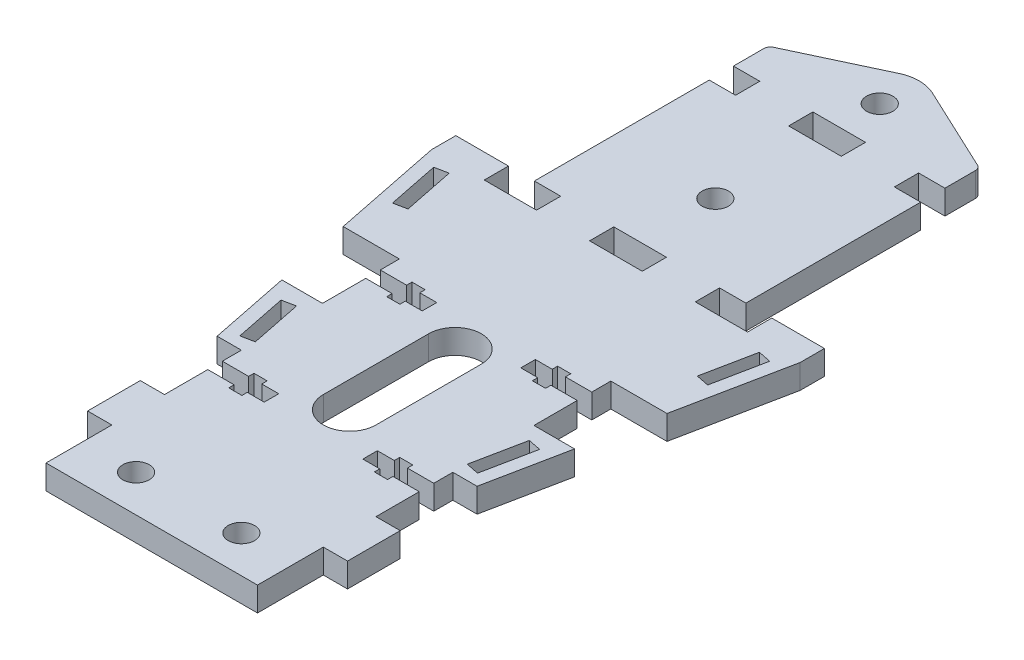
SolidWorks part; units mm, degrees
ref_plane "Front Plane" through (0, 0, 0) normal (0, 0, 1) x (1, 0, 0)
ref_plane "Top Plane" through (0, 0, 0) normal (0, 1, 0) x (1, 0, 0)
ref_plane "Right Plane" through (0, 0, 0) normal (1, 0, 0) x (0, 0, -1)
sketch "Sketch1" plane through (0, 0, 0) normal (0, 1, 0) x (1, 0, 0)
  line L0 (0, 90.3512) -> (0, 26.7242) construction
  line L1 (31.75, 26.7242) -> (25.5, 26.7242)
  line L2 (25.5, -85.217) -> (25.5, -69.342)
  line L3 (-25.5, -76.2964) -> (25.5, -76.2964) construction
  line L4 (0, 26.7242) -> (0, -76.2964) construction
  line L5 (25.5, -88.9) -> (-25.5, 88.9) construction
  line L6 (25.5, 88.9) -> (-25.5, -88.9) construction
  line L7 (-25.5, 77.6512) -> (25.5, 77.6512) construction
  line L8 (-25.5, -85.217) -> (-25.5, -69.342)
  line L9 (-25.5, 88.9) -> (-4.0485, 98.973)
  line L10 (-25.5, 80.5722) -> (-25.5, 88.9)
  line L11 (4.0485, 98.973) -> (25.5, 88.9)
  line L12 (-19.15, 74.7302) -> (-25.5, 74.7302)
  line L13 (-19.15, 74.7302) -> (-19.15, 80.5722)
  line L14 (-19.15, 80.5722) -> (-25.5, 80.5722)
  line L15 (19.15, 74.7302) -> (25.5, 74.7302)
  line L16 (-19.15, 74.7302) -> (-25.5, 80.5722) construction
  line L17 (-19.15, 80.5722) -> (-25.5, 74.7302) construction
  line L18 (6.35, 74.7302) -> (-6.35, 74.7302)
  line L19 (6.35, 74.7302) -> (6.35, 80.5722)
  line L20 (6.35, 80.5722) -> (-6.35, 80.5722)
  line L21 (-6.35, 74.7302) -> (-6.35, 80.5722)
  line L22 (6.35, 74.7302) -> (-6.35, 80.5722) construction
  line L23 (6.35, 80.5722) -> (-6.35, 74.7302) construction
  line L24 (19.15, 74.7302) -> (19.15, 80.5722)
  line L25 (19.15, 80.5722) -> (25.5, 80.5722)
  line L26 (25.5, 80.5722) -> (25.5, 88.9)
  line L27 (0, -76.2964) -> (0, -88.9) construction
  line L28 (0, -76.2964) -> (0, 26.7242) construction
  line L29 (0, -12.0861) -> (0, -37.4861) construction
  line L30 (6.35, -12.0861) -> (6.35, -37.4861)
  line L31 (-6.35, -12.0861) -> (-6.35, -37.4861)
  line L32 (-25.5, 53.6482) -> (25.5, 53.6482) construction
  line L33 (19.15, 32.5662) -> (25.5, 32.5662)
  line L34 (19.15, 32.5662) -> (19.15, 26.7242)
  line L35 (19.15, 26.7242) -> (25.5, 26.7242)
  line L36 (6.35, 32.5662) -> (6.35, 26.7242)
  line L37 (6.35, 32.5662) -> (-6.35, 32.5662)
  line L38 (6.35, 26.7242) -> (-6.35, 26.7242)
  line L39 (-6.35, 32.5662) -> (-6.35, 26.7242)
  line L40 (-19.15, 26.7242) -> (-25.5, 26.7242)
  line L41 (-19.15, 32.5662) -> (-19.15, 26.7242)
  line L42 (-19.15, 32.5662) -> (-25.5, 32.5662)
  line L43 (-25.5, 32.5662) -> (-25.5, 74.7302)
  line L44 (25.5, 32.5662) -> (25.5, 74.7302)
  line L45 (-44.45, 32.5662) -> (-31.75, 32.5662)
  line L46 (-31.75, 26.7242) -> (-25.5, 26.7242)
  line L47 (-44.45, 32.5662) -> (-44.45, 26.7242)
  line L48 (-25.5, -38.1) -> (-31.342, -38.1)
  line L49 (-31.75, 32.5662) -> (-31.75, 26.7242)
  line L50 (-44.45, 32.5662) -> (-31.75, 26.7242) construction
  line L51 (-44.45, 26.7242) -> (-31.75, 32.5662) construction
  line L52 (-31.342, -38.1) -> (-35.2968, -18.542)
  line L53 (-31.342, 0) -> (-39.0461, 0)
  line L54 (-31.342, -69.342) -> (-25.5, -69.342)
  line L55 (-31.342, -69.342) -> (-31.342, -56.642)
  line L56 (-31.342, -56.642) -> (-25.5, -56.642)
  line L57 (-25.5, -85.217) -> (25.5, -85.217)
  line L58 (-31.342, -69.342) -> (-25.5, -56.642) construction
  line L59 (-31.342, -56.642) -> (-25.5, -69.342) construction
  line L60 (-31.342, 0) -> (-25.5, 0)
  line L61 (-39.0461, 0) -> (-44.45, 26.7242)
  line L62 (-31.342, -18.542) -> (-25.5, -18.542)
  line L63 (-25.5, 0) -> (-25.5, -18.542)
  line L64 (-31.342, 0) -> (-25.5, -18.542) construction
  line L65 (-31.342, -18.542) -> (-25.5, 0) construction
  line L66 (-31.342, -18.542) -> (-35.2968, -18.542)
  line L67 (-25.5, -56.642) -> (-25.5, -38.1)
  line L68 (31.342, 0) -> (25.5, 0)
  line L69 (31.342, -18.542) -> (25.5, -18.542)
  line L70 (25.5, -38.1) -> (31.342, -38.1)
  line L71 (31.342, -69.342) -> (25.5, -69.342)
  line L72 (31.342, -56.642) -> (25.5, -56.642)
  line L73 (44.45, 26.7242) -> (31.75, 32.5662) construction
  line L74 (44.45, 32.5662) -> (31.75, 26.7242) construction
  line L75 (31.342, -18.542) -> (35.2968, -18.542)
  line L76 (39.0461, 0) -> (44.45, 26.7242)
  line L77 (31.342, -69.342) -> (31.342, -56.642)
  line L78 (31.342, 0) -> (39.0461, 0)
  line L79 (31.342, -38.1) -> (35.2968, -18.542)
  line L80 (31.75, 32.5662) -> (31.75, 26.7242)
  line L81 (44.45, 32.5662) -> (44.45, 26.7242)
  line L82 (44.45, 32.5662) -> (31.75, 32.5662)
  line L83 (25.5, -18.542) -> (25.5, 0)
  line L84 (25.5, -56.642) -> (25.5, -38.1)
  circle A0 centre (0, 90.3512) radius 3.175
  circle A1 centre (0, 50.7036) radius 3.175
  arc A4 (4.0485, 98.973) -> (-4.0485, 98.973) centre (0, 90.3512) ccw
  circle A5 centre (-12.7, -76.2964) radius 3.175
  circle A6 centre (12.7, -76.2964) radius 3.175
  arc A7 (6.35, -12.0861) -> (-6.35, -12.0861) centre (0, -12.0861) ccw
  arc A8 (-6.35, -37.4861) -> (6.35, -37.4861) centre (0, -37.4861) ccw
  point P0 (0, 0)
  point P14 (-38.1, 29.6452)
  point P17 (-6.35, 29.6452)
  point P21 (-22.325, 77.6512)
  point P28 (0, 77.6512)
  point P45 (0, -24.7861)
  point P66 (-28.421, -62.992)
  point P72 (-28.421, -9.271)
  point P97 (28.421, -9.271)
  point P98 (28.421, -62.992)
  point P99 (38.1, 29.6452)
  dimension "D3" = 6.35
  dimension "D4" = 6.35
  dimension "D5" = 39.6476
  dimension "D6" = 12.7
  dimension "D7" = 5.842
  dimension "D8" = 38.1
  dimension "D9" = 19.05
  dimension "D10" = 12.7
  dimension "D15" = 6.35
  dimension "D17" = 6.35
  dimension "D1" = 51
  dimension "D2" = 177.8
  dimension "D11" = 5.842
  dimension "D12" = 6.35
  dimension "D13" = 12.7
  dimension "D14" = 50.8
  dimension "D16" = 12.7
  dimension "D18" = 21.082
  dimension "D19" = 5.842
  dimension "D20" = 5.842
  dimension "D21" = 12.7
  dimension "D22" = 18.542
  dimension "D23" = 5.842
  dimension "D24" = 18.542
  dimension "D25" = 38.1
  dimension "D26" = 15.875
extrude "Boss-Extrude1" add sketch "Sketch1" along normal blind 5.842
sketch "Sketch2" plane through (0, 5.842, 0) normal (0, 1, 0) x (1, 0, 0)
  line L0 (0, 26.7242) -> (0, -85.217) construction
  line L1 (-6.35, 26.7242) -> (6.35, 26.7242) construction
  line L2 (-25.5, -85.217) -> (25.5, -85.217) construction
  line L3 (-25.5, -6.35) -> (25.5, -6.35) construction
  line L4 (-25.5, 0) -> (-25.5, -18.542) construction
  line L5 (25.5, -18.542) -> (25.5, 0) construction
  line L6 (-25.5, -44.45) -> (25.5, -44.45) construction
  line L7 (-25.5, -38.1) -> (-25.5, -56.642) construction
  line L8 (25.5, -56.642) -> (25.5, -38.1) construction
  line L9 (-39.0461, 0) -> (-25.5, 0) construction
  line L10 (-31.342, -38.1) -> (-25.5, -38.1) construction
  line L11 (-15.975, -42.6974) -> (-15.975, -41.402)
  line L12 (-19.15, -46.2026) -> (-25.5, -46.2026)
  line L13 (-1.3648, -6.35) -> (-1.3648, -44.45) construction
  line L14 (-19.15, -42.6974) -> (-25.5, -42.6974)
  line L15 (-25.5, -46.2026) -> (-25.5, -42.6974)
  line L16 (-19.15, -46.2026) -> (-25.5, -42.6974) construction
  line L17 (-19.15, -42.6974) -> (-25.5, -46.2026) construction
  line L18 (-15.975, -47.498) -> (-19.15, -47.498)
  line L19 (-15.975, -47.498) -> (-15.975, -46.2026)
  line L20 (-15.975, -41.402) -> (-19.15, -41.402)
  line L21 (-19.15, -47.498) -> (-19.15, -46.2026)
  line L22 (-15.975, -47.498) -> (-19.15, -41.402) construction
  line L23 (-15.975, -41.402) -> (-19.15, -47.498) construction
  line L24 (-11.892, -46.2026) -> (-15.975, -46.2026)
  line L25 (-11.892, -46.2026) -> (-11.892, -42.6974)
  line L26 (-11.892, -42.6974) -> (-15.975, -42.6974)
  line L27 (-19.15, -42.6974) -> (-19.15, -41.402)
  line L28 (-11.892, -46.2026) -> (-15.975, -42.6974) construction
  line L29 (-11.892, -42.6974) -> (-15.975, -46.2026) construction
  line L30 (-1.3648, -25.4) -> (0, -25.4) construction
  line L31 (-11.892, -8.1026) -> (-15.975, -4.5974) construction
  line L32 (-11.892, -4.5974) -> (-15.975, -8.1026) construction
  line L33 (-15.975, -9.398) -> (-19.15, -3.302) construction
  line L34 (-15.975, -3.302) -> (-19.15, -9.398) construction
  line L35 (-19.15, -8.1026) -> (-25.5, -4.5974) construction
  line L36 (-19.15, -4.5974) -> (-25.5, -8.1026) construction
  line L37 (-19.15, -8.1026) -> (-19.15, -9.398)
  line L38 (-11.892, -8.1026) -> (-15.975, -8.1026)
  line L39 (-11.892, -4.5974) -> (-11.892, -8.1026)
  line L40 (-11.892, -4.5974) -> (-15.975, -4.5974)
  line L41 (-19.15, -3.302) -> (-19.15, -4.5974)
  line L42 (-15.975, -9.398) -> (-19.15, -9.398)
  line L43 (-15.975, -3.302) -> (-15.975, -4.5974)
  line L44 (-15.975, -3.302) -> (-19.15, -3.302)
  line L45 (-25.5, -4.5974) -> (-25.5, -8.1026)
  line L46 (-19.15, -8.1026) -> (-25.5, -8.1026)
  line L47 (-19.15, -4.5974) -> (-25.5, -4.5974)
  line L48 (-15.975, -8.1026) -> (-15.975, -9.398)
  line L49 (19.15, -4.5974) -> (25.5, -8.1026) construction
  line L50 (19.15, -8.1026) -> (25.5, -4.5974) construction
  line L51 (15.975, -3.302) -> (19.15, -9.398) construction
  line L52 (15.975, -9.398) -> (19.15, -3.302) construction
  line L53 (11.892, -4.5974) -> (15.975, -8.1026) construction
  line L54 (11.892, -8.1026) -> (15.975, -4.5974) construction
  line L55 (11.892, -42.6974) -> (15.975, -46.2026) construction
  line L56 (11.892, -46.2026) -> (15.975, -42.6974) construction
  line L57 (15.975, -41.402) -> (19.15, -47.498) construction
  line L58 (15.975, -47.498) -> (19.15, -41.402) construction
  line L59 (19.15, -42.6974) -> (25.5, -46.2026) construction
  line L60 (19.15, -46.2026) -> (25.5, -42.6974) construction
  line L61 (15.975, -8.1026) -> (15.975, -9.398)
  line L62 (19.15, -4.5974) -> (25.5, -4.5974)
  line L63 (19.15, -8.1026) -> (25.5, -8.1026)
  line L64 (25.5, -4.5974) -> (25.5, -8.1026)
  line L65 (15.975, -3.302) -> (19.15, -3.302)
  line L66 (15.975, -3.302) -> (15.975, -4.5974)
  line L67 (15.975, -9.398) -> (19.15, -9.398)
  line L68 (19.15, -3.302) -> (19.15, -4.5974)
  line L69 (11.892, -4.5974) -> (15.975, -4.5974)
  line L70 (11.892, -4.5974) -> (11.892, -8.1026)
  line L71 (11.892, -8.1026) -> (15.975, -8.1026)
  line L72 (19.15, -8.1026) -> (19.15, -9.398)
  line L73 (19.15, -42.6974) -> (19.15, -41.402)
  line L74 (11.892, -42.6974) -> (15.975, -42.6974)
  line L75 (11.892, -46.2026) -> (11.892, -42.6974)
  line L76 (11.892, -46.2026) -> (15.975, -46.2026)
  line L77 (19.15, -47.498) -> (19.15, -46.2026)
  line L78 (15.975, -41.402) -> (19.15, -41.402)
  line L79 (15.975, -47.498) -> (15.975, -46.2026)
  line L80 (15.975, -47.498) -> (19.15, -47.498)
  line L81 (25.5, -46.2026) -> (25.5, -42.6974)
  line L82 (19.15, -42.6974) -> (25.5, -42.6974)
  line L83 (19.15, -46.2026) -> (25.5, -46.2026)
  line L84 (15.975, -42.6974) -> (15.975, -41.402)
  point P22 (-22.325, -44.45)
  point P27 (-17.5625, -44.45)
  point P32 (-13.9335, -44.45)
  point P53 (-13.9335, -6.35)
  point P54 (-17.5625, -6.35)
  point P55 (-22.325, -6.35)
  point P80 (22.325, -6.35)
  point P81 (17.5625, -6.35)
  point P82 (13.9335, -6.35)
  point P83 (13.9335, -44.45)
  point P84 (17.5625, -44.45)
  point P85 (22.325, -44.45)
  dimension "D1" = 6.35
  dimension "D2" = 6.35
  dimension "D3" = 3.5052
  dimension "D4" = 6.35
  dimension "D5" = 6.096
  dimension "D6" = 3.175
  dimension "D7" = 4.083
extrude "Cut-Extrude1" cut sketch "Sketch2" against normal through all
fillet "Fillet1" radius 1.5875 2 edges at (25.5, 2.921, -88.9) (-25.5, 2.921, -88.9)
sketch "Sketch3" plane through (0, 5.842, 0) normal (0, 1, 0) x (1, 0, 0)
  line L0 (-44.45, 26.7242) -> (44.45, 26.7242) construction
  line L1 (-31.342, -38.1) -> (31.342, -38.1) construction
  line L2 (-39.5911, 26.7242) -> (-26.4831, -38.1) construction
  line L3 (-35.2968, -18.542) -> (-31.342, -38.1) construction
  line L4 (0, 26.7242) -> (0, -38.1) construction
  line L5 (-40.5178, 23.2976) -> (-38.0007, 10.8495)
  line L6 (-40.5178, 23.2976) -> (-37.4058, 23.9269)
  line L7 (-38.0007, 10.8495) -> (-34.8887, 11.4788)
  line L8 (-37.4058, 23.9269) -> (-34.8887, 11.4788)
  line L9 (-40.5178, 23.2976) -> (-34.8887, 11.4788) construction
  line L10 (-38.0007, 10.8495) -> (-37.4058, 23.9269) construction
  line L11 (-29.1374, -4.8993) -> (-36.9368, -6.4764) construction
  line L12 (-31.1855, -22.8546) -> (-25.5564, -34.6733) construction
  line L13 (-28.6684, -35.3026) -> (-28.0735, -22.2253) construction
  line L14 (-25.5564, -34.6733) -> (-28.0735, -22.2253)
  line L15 (-31.1855, -22.8546) -> (-28.0735, -22.2253)
  line L16 (-28.6684, -35.3026) -> (-25.5564, -34.6733)
  line L17 (-28.6684, -35.3026) -> (-31.1855, -22.8546)
  line L18 (28.6684, -35.3026) -> (28.0735, -22.2253) construction
  line L19 (31.1855, -22.8546) -> (25.5564, -34.6733) construction
  line L20 (29.1374, -4.8993) -> (36.9368, -6.4764) construction
  line L21 (38.0007, 10.8495) -> (37.4058, 23.9269) construction
  line L22 (40.5178, 23.2976) -> (34.8887, 11.4788) construction
  line L23 (39.5911, 26.7242) -> (26.4831, -38.1) construction
  line L24 (28.6684, -35.3026) -> (31.1855, -22.8546)
  line L25 (28.6684, -35.3026) -> (25.5564, -34.6733)
  line L26 (31.1855, -22.8546) -> (28.0735, -22.2253)
  line L27 (25.5564, -34.6733) -> (28.0735, -22.2253)
  line L28 (37.4058, 23.9269) -> (34.8887, 11.4788)
  line L29 (38.0007, 10.8495) -> (34.8887, 11.4788)
  line L30 (40.5178, 23.2976) -> (37.4058, 23.9269)
  line L31 (40.5178, 23.2976) -> (38.0007, 10.8495)
  point P15 (-37.7033, 17.3882)
  point P22 (-33.0371, -5.6879)
  point P26 (-28.3709, -28.764)
  point P39 (28.3709, -28.764)
  point P40 (33.0371, -5.6879)
  point P41 (37.7033, 17.3882)
  dimension "D1" = 4.7625
  dimension "D2" = 3.175
  dimension "D3" = 12.7
  dimension "D4" = 9.525
extrude "Cut-Extrude2" cut sketch "Sketch3" against normal through all
